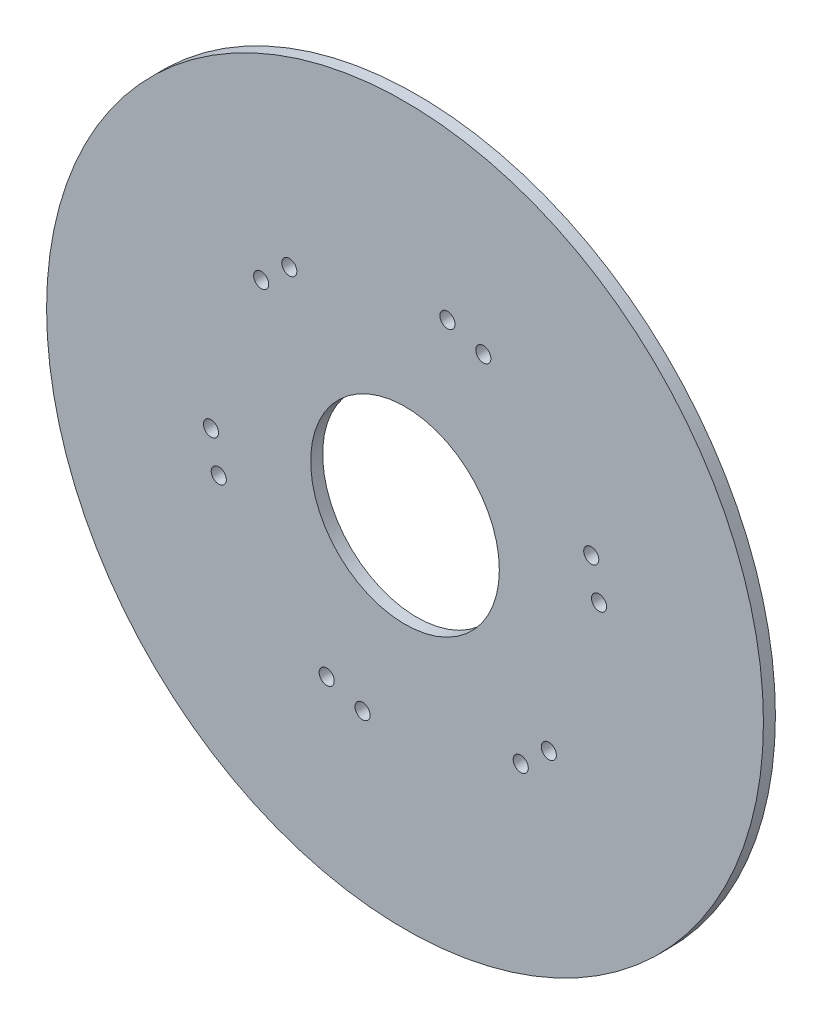
SolidWorks part; units mm, degrees
ref_plane "Front Plane" through (0, 0, 0) normal (0, 0, 1) x (1, 0, 0)
ref_plane "Top Plane" through (0, 0, 0) normal (0, 1, 0) x (1, 0, 0)
ref_plane "Right Plane" through (0, 0, 0) normal (1, 0, 0) x (0, 0, -1)
sketch "Sketch1" plane through (0, 0, 0) normal (0, 0, 1) x (1, 0, 0)
  circle A0 centre (0, 0) radius 95
  circle A1 centre (0, 0) radius 25
  dimension "D1" = 190
  dimension "D2" = 50
extrude "Boss-Extrude1" add sketch "Sketch1" along normal blind 3.175 contours A0 A1 region at (-92.313, 0, 0)
sketch "Sketch2" plane through (0, 0, 0) normal (0, 0, -1) x (-1, 0, 0)
  circle A0 centre (-49.3631, 15.5091) radius 2
  circle A1 centre (-51.4246, 5.7238) radius 2
  circle A2 centre (-38.1128, -34.9952) radius 2
  circle A3 centre (-30.6693, -41.6731) radius 2
  circle A4 centre (11.2503, -50.5043) radius 2
  circle A5 centre (20.7553, -47.3969) radius 2
  circle A6 centre (49.3631, -15.5091) radius 2
  circle A7 centre (51.4246, -5.7238) radius 2
  circle A8 centre (38.1128, 34.9952) radius 2
  circle A9 centre (30.6693, 41.6731) radius 2
  circle A10 centre (-20.7553, 47.3969) radius 2
  circle A11 centre (-11.2503, 50.5043) radius 2
extrude "Cut-Extrude1" cut sketch "Sketch2" against normal through all
